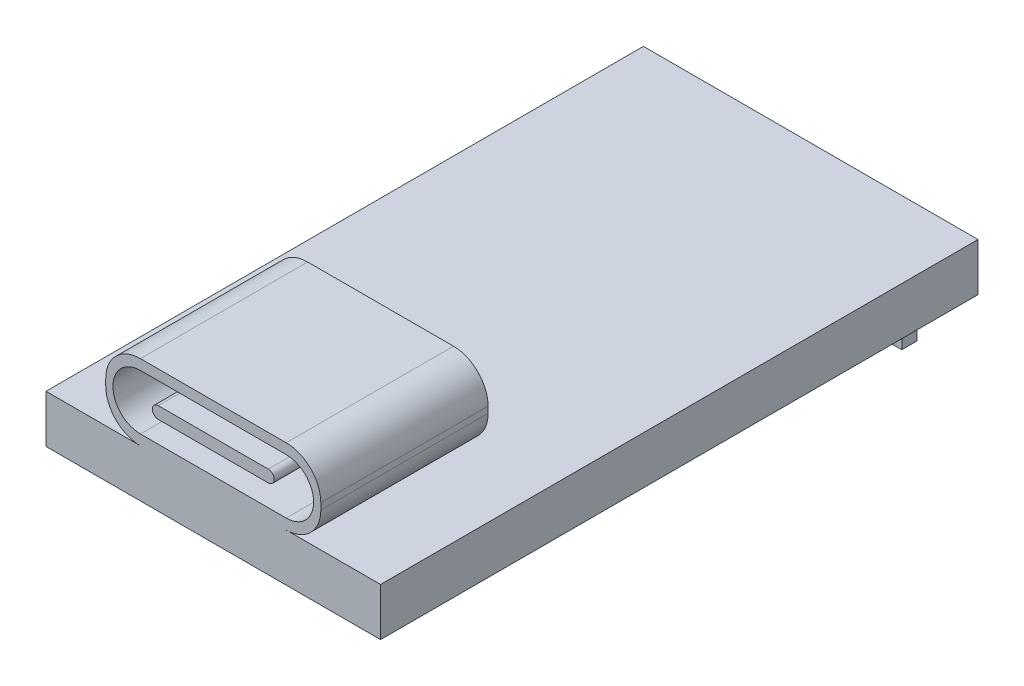
SolidWorks part; units mm, degrees
ref_plane "Front Plane" through (0, 0, 0) normal (0, 0, 1) x (1, 0, 0)
ref_plane "Top Plane" through (0, 0, 0) normal (0, 1, 0) x (1, 0, 0)
ref_plane "Right Plane" through (0, 0, 0) normal (1, 0, 0) x (0, 0, -1)
sketch "Sketch1" plane through (0, 0, 0) normal (0, 1, 0) x (1, 0, 0)
  line L1 (0, 0) -> (14, 0)
  line L2 (0, 0) -> (0, 25)
  line L3 (0, 25) -> (14, 25)
  line L4 (14, 0) -> (14, 25)
  dimension "D1" = 14
  dimension "D2" = 25
extrude "Boss-Extrude1" add sketch "Sketch1" along normal blind 2
sketch "Sketch2" plane through (0, 2, 0) normal (0, 1, 0) x (1, 0, 0)
  line L0 (0, 0) -> (14, 0) construction
  line L1 (2.5, 0) -> (11.5, 0)
  line L2 (2.5, 0) -> (2.5, 7)
  line L3 (2.5, 7) -> (11.5, 7)
  line L4 (11.5, 0) -> (11.5, 7)
  line L5 (11.5, 3.5) -> (14, 3.5) construction
  line L6 (14, 0) -> (14, 25) construction
  line L7 (2.5, 3.5) -> (0, 3.5) construction
  line L8 (0, 25) -> (0, 0) construction
  dimension "D1" = 9
  dimension "D2" = 7
extrude "Boss-Extrude2" add sketch "Sketch2" along normal blind 3.16
sketch "Sketch3" plane through (0, 0, 0) normal (0, 0, 1) x (1, 0, 0)
  line L0 (7, 5.16) -> (7, 3.58) construction
  line L1 (2.5, 5.16) -> (11.5, 5.16) construction
  line L2 (7, 3.58) -> (7, 2) construction
  line L3 (7, 2) -> (10.05, 2)
  line L4 (7, 2) -> (3.95, 2)
  line L5 (2.5, 3.45) -> (2.5, 3.71)
  line L6 (2.5, 5.16) -> (2.5, 2) construction
  line L7 (3.95, 5.16) -> (10.05, 5.16)
  line L8 (11.5, 3.71) -> (11.5, 3.45)
  line L9 (10.05, 5.16) -> (11.5, 5.16)
  line L10 (11.5, 5.16) -> (11.5, 3.71)
  line L11 (11.5, 3.45) -> (11.5, 2)
  line L12 (11.5, 2) -> (10.05, 2)
  line L13 (3.95, 2) -> (2.5, 2)
  line L14 (2.5, 2) -> (2.5, 3.45)
  line L15 (2.5, 3.71) -> (2.5, 5.16)
  line L16 (2.5, 5.16) -> (3.95, 5.16)
  arc A0 (11.5, 3.71) -> (10.05, 5.16) centre (10.05, 3.71) ccw
  arc A1 (11.5, 3.45) -> (10.05, 2) centre (10.05, 3.45) cw
  arc A2 (2.5, 3.45) -> (3.95, 2) centre (3.95, 3.45) ccw
  arc A3 (2.5, 3.71) -> (3.95, 5.16) centre (3.95, 3.71) cw
  point P18 (11.5, 5.16)
  point P25 (2.5, 5.16)
  line M6 (11.5, 2) -> (11.5, 5.16)
  line M7 (11.5, 5.16) -> (2.5, 5.16)
  line M8 (2.5, 5.16) -> (2.5, 2)
  dimension "D2" = 1.45
  dimension "D1" = 1.58
extrude "Cut-Extrude1" cut sketch "Sketch3" against normal blind 7.16 contours A2 L13 M8 | A3 M8 M7 | A0 M6 M7 | A1 L12 M6 region at (11.1761, 2.3239, 0) region at (2.8239, 2.3239, 0) region at (11.1761, 4.8361, 0) region at (2.8239, 4.8361, 0)
sketch "Sketch4" plane through (0, 0, 0) normal (0, 0, 1) x (1, 0, 0)
  line L0 (3.95, 5.16) -> (3.95, 2) construction
  line L1 (10.05, 5.16) -> (10.05, 2) construction
  line L2 (3.95, 3.58) -> (10.05, 3.58) construction
  line L3 (3.95, 3.83) -> (10.05, 3.83)
  line L4 (3.95, 3.33) -> (10.05, 3.33)
  line L5 (3.95, 3.58) -> (10.05, 3.58) construction
  line L6 (3.95, 4.73) -> (10.05, 4.73)
  line L7 (3.95, 2.43) -> (10.05, 2.43)
  arc A0 (3.95, 3.83) -> (3.95, 3.33) centre (3.95, 3.58) ccw
  arc A1 (10.05, 3.33) -> (10.05, 3.83) centre (10.05, 3.58) ccw
  arc A2 (3.95, 4.73) -> (3.95, 2.43) centre (3.95, 3.58) ccw
  arc A3 (10.05, 2.43) -> (10.05, 4.73) centre (10.05, 3.58) ccw
  point P7 (7, 3.58)
  point P17 (7, 3.58)
  dimension "D1" = 0.5
  dimension "D2" = 2.3
extrude "Cut-Extrude2" cut sketch "Sketch4" against normal blind 2.16
sketch "Sketch5" plane through (0, 0, 0) normal (0, 0, 1) x (1, 0, 0)
  line L0 (3.7, 3.58) -> (4.7, 3.58) construction
  line L1 (10.3, 3.58) -> (9.3, 3.58) construction
  line L2 (4.7, 3.58) -> (9.3, 3.58) construction
  line L3 (4.7, 3.83) -> (9.3, 3.83)
  line L4 (4.7, 3.33) -> (9.3, 3.33)
  line L6 (10.05, 3.83) -> (3.95, 3.83) construction
  line L7 (3.95, 3.58) -> (10.05, 3.58) construction
  line L8 (3.95, 3.83) -> (10.05, 3.83)
  line L9 (3.95, 3.33) -> (10.05, 3.33)
  arc A0 (3.95, 3.83) -> (3.95, 3.33) centre (3.95, 3.58) ccw construction
  arc A1 (10.05, 3.33) -> (10.05, 3.83) centre (10.05, 3.58) ccw construction
  arc A2 (4.7, 3.83) -> (4.7, 3.33) centre (4.7, 3.58) ccw
  arc A3 (9.3, 3.33) -> (9.3, 3.83) centre (9.3, 3.58) ccw
  arc A4 (3.95, 3.83) -> (3.95, 3.33) centre (3.95, 3.58) ccw
  arc A5 (10.05, 3.33) -> (10.05, 3.83) centre (10.05, 3.58) ccw
  point P10 (7, 3.58)
  point P21 (7, 3.58)
  arc M7 (3.95, 3.83) -> (3.95, 3.33) centre (3.95, 3.58) ccw
  line M8 (3.95, 3.33) -> (10.05, 3.33)
  arc M9 (10.05, 3.33) -> (10.05, 3.83) centre (10.05, 3.58) ccw
  line M10 (10.05, 3.83) -> (3.95, 3.83)
  dimension "D1" = 1
extrude "Cut-Extrude3" cut sketch "Sketch5" against normal blind 2.16 contours A2 M10 M7 M8 | A3 M8 M9 M10 region at (4.1287, 3.58, 0) region at (9.8713, 3.58, 0)
sketch "Sketch7" plane through (0, 0, 0) normal (0, -1, 0) x (1, 0, 0)
  line L0 (0, -23.73) -> (1.92, -23.73) construction
  line L1 (0, -25) -> (0, 0) construction
  line L2 (14, -23.73) -> (12.08, -23.73) construction
  line L3 (14, 0) -> (14, -25) construction
  line L4 (14, -25) -> (0, -25) construction
  line L5 (1.6, -24.05) -> (2.24, -24.05)
  line L6 (1.6, -24.05) -> (1.6, -23.41)
  line L7 (1.6, -23.41) -> (2.24, -23.41)
  line L8 (2.24, -24.05) -> (2.24, -23.41)
  line L9 (1.6, -24.05) -> (2.24, -23.41) construction
  line L10 (1.6, -23.41) -> (2.24, -24.05) construction
  line L11 (0.65, -25) -> (3.19, -25)
  line L12 (0.65, -25) -> (0.65, -22.46)
  line L13 (0.65, -22.46) -> (3.19, -22.46)
  line L14 (3.19, -25) -> (3.19, -22.46)
  line L15 (0.65, -25) -> (3.19, -22.46) construction
  line L16 (0.65, -22.46) -> (3.19, -25) construction
  line L17 (4.78, -24.05) -> (4.78, -23.41)
  line L18 (4.14, -24.05) -> (4.78, -24.05)
  line L19 (4.14, -24.05) -> (4.14, -23.41)
  line L20 (4.14, -23.41) -> (4.78, -23.41)
  line L21 (7.32, -24.05) -> (7.32, -23.41)
  line L22 (6.68, -24.05) -> (7.32, -24.05)
  line L23 (6.68, -24.05) -> (6.68, -23.41)
  line L24 (6.68, -23.41) -> (7.32, -23.41)
  line L25 (9.86, -24.05) -> (9.86, -23.41)
  line L26 (9.22, -24.05) -> (9.86, -24.05)
  line L27 (9.22, -24.05) -> (9.22, -23.41)
  line L28 (9.22, -23.41) -> (9.86, -23.41)
  line L29 (12.08, -23.41) -> (12.08, -24.05) construction
  line L30 (12.08, -24.05) -> (12.08, -23.73) construction
  line L31 (12.08, -23.73) -> (12.4, -23.73) construction
  line L32 (12.4, -24.05) -> (12.4, -23.41)
  line L33 (11.76, -24.05) -> (12.4, -24.05)
  line L34 (11.76, -24.05) -> (11.76, -23.41)
  line L35 (11.76, -23.41) -> (12.4, -23.41)
  dimension "D1" = 0.64
  dimension "D2" = 2.54
  dimension "D4" = 1.92
  dimension "D3" = 5
extrude "Boss-Extrude3" add sketch "Sketch7" along normal blind 2 contours L20 L19 L18 L17 | L24 L23 L22 L21 | L28 L27 L26 L25 | L35 L34 L33 L32 | L8 L7 L6 L5 region at (4.46, 0, -23.73) region at (7, 0, -23.73) region at (9.54, 0, -23.73) region at (12.08, 0, -23.73)
